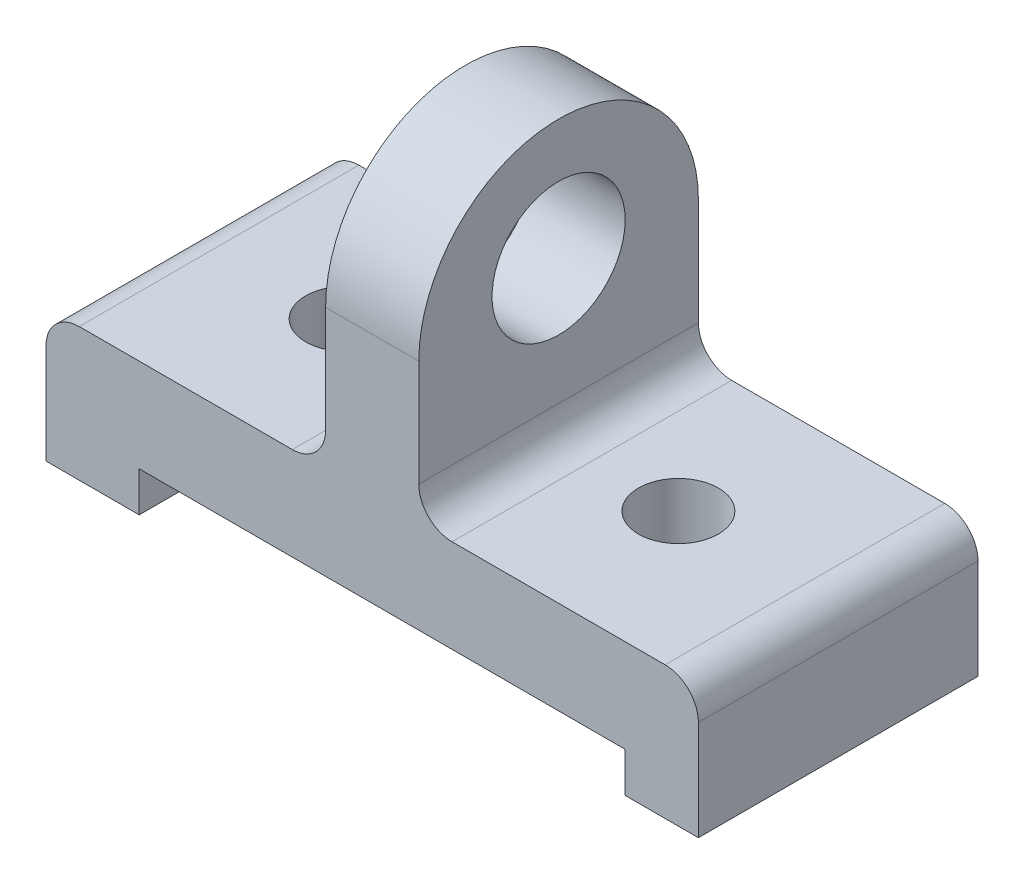
SolidWorks part; units mm, degrees
ref_plane "Front Plane" through (0, 0, 0) normal (0, 0, 1) x (1, 0, 0)
ref_plane "Top Plane" through (0, 0, 0) normal (0, 1, 0) x (1, 0, 0)
ref_plane "Right Plane" through (0, 0, 0) normal (1, 0, 0) x (0, 0, -1)
sketch "Sketch1" plane through (0, 0, 0) normal (0, 1, 0) x (1, 0, 0)
  line L0 (0, 28.0456) -> (0, -44.3392) construction
  line L1 (-49, 21) -> (49, 21)
  line L2 (-49, 21) -> (-49, -21)
  line L3 (-49, -21) -> (49, -21)
  line L4 (49, 21) -> (49, -21)
  line L5 (-49, 21) -> (49, -21) construction
  line L6 (-49, -21) -> (49, 21) construction
  point P0 (0, 0)
  dimension "D1" = 98
  dimension "D2" = 42
extrude "Boss-Extrude1" add sketch "Sketch1" along normal blind 14
sketch "Sketch2" plane through (0, 0, 0) normal (0, 0, 1) x (1, 0, 0)
  line L0 (49, 0) -> (49, -6)
  line L1 (49, -6) -> (37.9824, -6)
  line L2 (37.9824, -6) -> (37.9824, 0)
  line L3 (-49, 0) -> (49, 0) construction
  line L4 (37.9824, 0) -> (49, 0)
  dimension "D1" = 6
  dimension "D2" = 11.0176
extrude "Boss-Extrude2" add sketch "Sketch2" along normal blind 21 and the other way blind 21
fillet "Fillet1" radius 5 1 edges at (49, 14, 0)
sketch "Sketch3" plane through (0, 0, 21) normal (0, 0, 1) x (1, 0, 0)
  line L0 (-49, 0) -> (-49, -6)
  line L1 (-49, -6) -> (-35, -6)
  line L2 (-35, -6) -> (-35, 0)
  line L3 (-49, 0) -> (37.9824, 0) construction
  line L4 (-35, 0) -> (-49, 0)
  line L5 (-49, 14) -> (-49, 0) construction
  point P9 (0, 0)
  dimension "D1" = 14
  dimension "D2" = 6
extrude "Boss-Extrude3" add sketch "Sketch3" against normal blind 42
fillet "Fillet2" radius 5 1 edges at (-49, 14, 0)
sketch "Sketch4" plane through (0, 0, 0) normal (0, 1, 0) x (1, 0, 0)
  line L0 (-44, -21) -> (44, -21) construction
  line L1 (49, 21) -> (49, -21) construction
  line L2 (0, 36.0537) -> (0, -35.7569) construction
  circle A0 centre (25, 0) radius 6
  circle A1 centre (-25, 0) radius 6
  dimension "D1" = 12
  dimension "D2" = 21
  dimension "D3" = 24
extrude "Cut-Extrude1" cut sketch "Sketch4" along normal blind 14
sketch "Sketch5" plane through (0, 0, 0) normal (1, 0, 0) x (0, 0, -1)
  line L0 (-21, 14) -> (-21, 35)
  line L1 (0, 37.8958) -> (0, -21.0606) construction
  line L2 (-21, 14) -> (21, 14) construction
  line L3 (21, 14) -> (21, 35)
  line L4 (21, 14) -> (-21, 14)
  arc A0 (-21, 35) -> (21, 35) centre (0, 35) cw
  circle A1 centre (0, 37.8958) radius 10
  dimension "D2" = 20
  dimension "D1" = 21
extrude "Boss-Extrude4" add sketch "Sketch5" along normal blind 7 and the other way blind 7
fillet "Fillet3" radius 5 1 edges at (7, 14, 0)
fillet "Fillet4" radius 5 1 edges at (-7, 14, 0)
